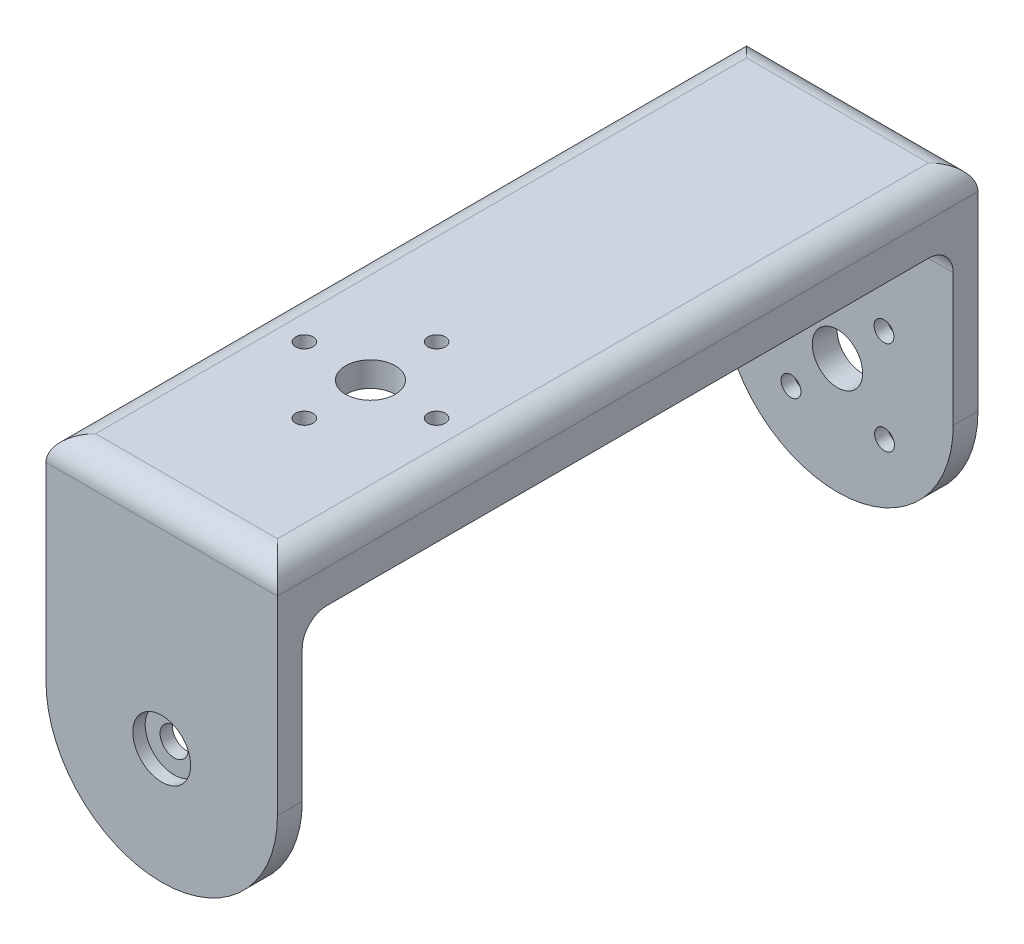
SolidWorks part; units mm, degrees
ref_plane "Plano frontal" through (0, 0, 0) normal (0, 0, 1) x (1, 0, 0)
ref_plane "Plano superior" through (0, 0, 0) normal (0, 1, 0) x (1, 0, 0)
ref_plane "Plano direito" through (0, 0, 0) normal (1, 0, 0) x (0, 0, -1)
sketch "Esboço1" plane through (0, 0, 0) normal (0, 0, 1) x (1, 0, 0)
  line L1 (16.6635, 58.1054) -> (-7.3365, 58.1054)
  line L3 (-7.3365, 58.1054) -> (-9.3365, 58.1054)
  line L6 (-9.3365, 58.1054) -> (-9.3365, 32.1054)
  line L7 (16.6635, 58.1054) -> (18.6635, 58.1054)
  line L8 (18.6635, 58.1054) -> (18.6635, 32.1054)
  line L9 (4.6635, 58.1054) -> (4.6635, 32.1054) construction
  arc A2 (-9.3365, 32.1054) -> (18.6635, 32.1054) centre (4.6635, 32.1054) ccw
  circle A9 centre (4.6635, 32.1054) radius 3.05 construction
  circle A10 centre (4.6635, 32.1054) radius 3.05
  dimension "D1" = 26
  dimension "D2" = 2
  dimension "D3" = 2
  dimension "D4" = 24
extrude "Ressalto-extrusão1" add sketch "Esboço1" against normal blind 3
hole_wizard "Rebaixo para parafuso com cabeça redonda de M21" positions "Esboço10" profile "Esboço11" counterbore size "M2" standard "DIN" end condition up to next
sketch "Esboço10" plane through (0, 0, -3) normal (0, 0, -1) x (-1, 0, 0)
  circle A0 centre (-10.2882, 37.7942) radius 1.025 construction
  point P0 (-10.2882, 37.7942)
sketch "Esboço11" plane through (10.2882, 37.7942, -3) normal (1, 0, 0) x (0, 1, 0)
  line L0 (0, 0) -> (0, 3)
  line L1 (0, 3) -> (1.2, 3)
  line L3 (1.2, 3) -> (1.2, 1.4)
  line L4 (1.2, 1.4) -> (2.2, 1.4)
  line L5 (2.2, 1.4) -> (2.2, 0)
  line L7 (2.2, 0) -> (0, 0)
  line L11 (0, -6.35) -> (0, 107.95) construction
  dimension "Thru Hole Dia." = 2.4
  dimension "Thru Hole Depth" = 3
  dimension "C'Bore Dia." = 4.4
  dimension "C'Bore Depth" = 1.4
pattern_circular "PadrãoCircular1" count 4 over 360 about axis through (4.6635, 32.1054, -3) along (0, 0, 1) of "Rebaixo para parafuso com cabeça redonda de M21"
sketch "Sketch6" plane through (0, 0, 0) normal (0, 0, 1) x (1, 0, 0)
  line L0 (-9.3365, 58.1054) -> (-9.3365, 55.1054)
  line L1 (-9.3365, 58.1054) -> (-9.3365, 32.1054) construction
  line L2 (-9.3365, 55.1054) -> (18.6635, 55.1054)
  line L3 (18.6635, 32.1054) -> (18.6635, 58.1054) construction
  line L4 (18.6635, 55.1054) -> (18.6635, 58.1054)
  line L5 (18.6635, 58.1054) -> (-9.3365, 58.1054)
  dimension "D1" = 3
extrude "Boss-Extrude2" add sketch "Sketch6" along normal offset from surface (78.75 mm away) 0.25 offset beyond the face yes
sketch "Sketch8" plane through (0, 0, 78.75) normal (0, 0, 1) x (1, 0, 0)
  line L0 (-9.3365, 58.1054) -> (18.6635, 58.1054)
  line L1 (18.6635, 58.1054) -> (18.6635, 55.1054)
  line L2 (18.6635, 55.1054) -> (-9.3365, 55.1054)
  line L3 (-9.3365, 55.1054) -> (-9.3365, 58.1054)
extrude "Boss-Extrude3" add sketch "Sketch8" along normal blind 3
sketch "Sketch9" plane through (0, 55.1054, 0) normal (0, -1, 0) x (1, 0, 0)
  line L0 (-9.3365, 81.75) -> (-9.3365, 78.75) construction
  line L1 (-9.3365, 81.75) -> (-9.3365, 0) construction
  line L2 (-9.3365, 78.75) -> (-9.3365, 0) construction
  line L3 (-9.3365, 39.375) -> (18.6635, 39.375) construction
  line L4 (18.6635, 81.75) -> (18.6635, 0) construction
  dimension "D1" = 3
ref_plane "Plane1" through (0, 0, 39.375) normal (0, 0, -1) x (-1, 0, 0)
mirror "Mirror1" about plane through (0, 0, 39.375) normal (0, 0, -1) of "Ressalto-extrusão1"
sketch "Sketch10" plane through (0, 0, 81.75) normal (0, 0, 1) x (1, 0, 0)
  circle A0 centre (4.6635, 32.1054) radius 3.05
  arc A1 (-9.3365, 32.1054) -> (18.6635, 32.1054) centre (4.6635, 32.1054) ccw construction
  dimension "D1" = 6.1
extrude "Boss-Extrude4" add sketch "Sketch10" against normal blind 3
sketch "Sketch12" plane through (0, 0, 81.75) normal (0, 0, 1) x (1, 0, 0)
  circle A0 centre (4.6635, 32.1054) radius 3.5
  arc A1 (-9.3365, 32.1054) -> (18.6635, 32.1054) centre (4.6635, 32.1054) ccw construction
  dimension "D2" = 7
extrude "Cut-Extrude3" cut sketch "Sketch12" against normal blind 1.5
sketch "Sketch13" plane through (0, 0, 80.25) normal (0, 0, 1) x (1, 0, 0)
  circle A0 centre (4.6635, 32.1054) radius 1.7
  dimension "D1" = 3.4
extrude "Cut-Extrude4" cut sketch "Sketch13" against normal blind 1.5
sketch "Sketch15" plane through (0, 58.1054, 0) normal (0, 1, 0) x (1, 0, 0)
  line L0 (4.6635, -56.5) -> (4.6635, -64.5) construction
  line L1 (-6.3365, -64.5) -> (-6.3365, -48.5) construction
  line L2 (-6.3365, -64.5) -> (-6.3365, -48.5) construction
  line L3 (-6.3365, -56.5) -> (4.6635, -56.5) construction
  line L4 (18.6635, -81.75) -> (-9.3365, -81.75) construction
  circle A1 centre (4.6635, -64.5) radius 1.05
  circle A2 centre (-3.3365, -56.5) radius 1.05
  circle A3 centre (4.6635, -48.5) radius 1.05
  circle A4 centre (12.6635, -56.5) radius 1.05
  circle A5 centre (4.6635, -56.5) radius 3
  point P14 (4.6635, -56.5)
  point P18 (4.6635, -81.75)
  dimension "D1" = 8
  dimension "D2" = 2.1
  dimension "D4" = 6
  dimension "D3" = 4
extrude "Cut-Extrude5" cut sketch "Sketch15" against normal blind 3
sketch "Esboço12" plane through (-9.3365, 0, 0) normal (-1, 0, 0) x (0, 0, 1)
  line L0 (81.75, 58.1054) -> (81.75, 32.1054) construction
  line L1 (-3, 58.1054) -> (81.75, 58.1054)
  line L2 (-3, 58.1054) -> (-3, 51.1054)
  line L3 (-3, 51.1054) -> (81.75, 51.1054)
  line L4 (81.75, 58.1054) -> (81.75, 51.1054)
  dimension "D1" = 7
extrude "Ressalto-extrusão2" add sketch "Esboço12" against normal blind 3
sketch "Esboço13" plane through (18.6635, 0, 0) normal (1, 0, 0) x (0, 0, -1)
  line L0 (3, 32.1054) -> (3, 58.1054) construction
  line L1 (-81.75, 58.1054) -> (3, 58.1054)
  line L2 (-81.75, 58.1054) -> (-81.75, 51.1054)
  line L3 (-81.75, 51.1054) -> (3, 51.1054)
  line L4 (3, 58.1054) -> (3, 51.1054)
  line L5 (0, 51.1054) -> (-78.75, 51.1054) construction
extrude "Ressalto-extrusão3" add sketch "Esboço13" against normal blind 3
fillet "Fillet2" radius 3 16 edges at (4.6635, 55.1054, 0) (4.6635, 55.1054, 78.75) (4.6635, 58.1054, 81.75) (4.6635, 58.1054, -3) (-9.3365, 58.1054, 39.375) (18.6635, 58.1054, 39.375) (-6.3365, 55.1054, 39.375) (15.6635, 55.1054, 39.375) (17.1635, 51.1054, 78.75) (-7.8365, 51.1054, 78.75) (17.1635, 51.1054, 0) (-7.8365, 51.1054, 0) (-6.3365, 53.1054, 0) (-6.3365, 53.1054, 78.75) (15.6635, 53.1054, 78.75) (15.6635, 53.1054, 0)
